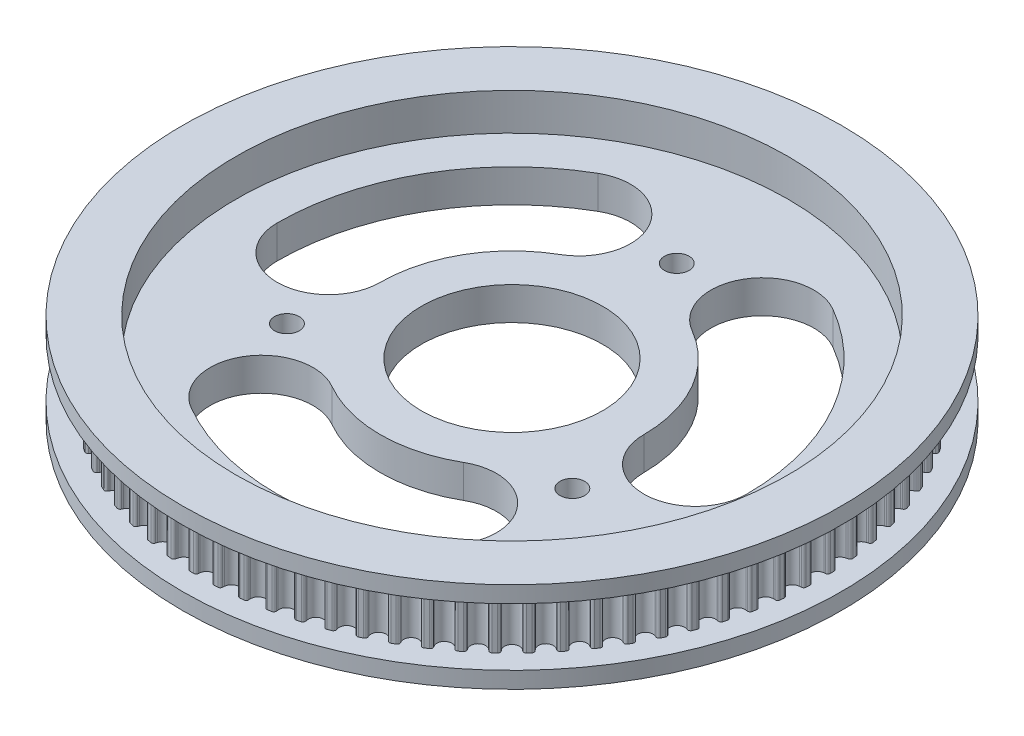
SolidWorks part; units mm, degrees
material "6061 合金"
ref_plane "前视基准面" through (0, 0, 0) normal (0, 0, 1) x (1, 0, 0)
ref_plane "上视基准面" through (0, 0, 0) normal (0, 1, 0) x (1, 0, 0)
ref_plane "右视基准面" through (0, 0, 0) normal (1, 0, 0) x (0, 0, -1)
sketch "草图1" plane through (0, 0, 0) normal (0, 1, 0) x (1, 0, 0)
  circle A0 centre (0, 0) radius 40
  dimension "D1" = 80
extrude "凸台-拉伸1" add sketch "草图1" along normal mid plane 11
sketch "草图2" plane through (0, 0, 0) normal (0, 1, 0) x (1, 0, 0)
  line L0 (0, 0) -> (0, 37.815) construction
  line L1 (-0.9274, 37.1503) -> (-0.9032, 36.9531)
  line L2 (0.9274, 37.1503) -> (0.9032, 36.9531)
  line L3 (-0.95, 37.2332) -> (0.95, 37.2332) construction
  line L4 (1.9902, 37.1086) -> (1.9989, 36.9101)
  line L5 (3.8394, 36.9631) -> (3.7997, 36.7683)
  line L6 (4.8956, 36.838) -> (4.8886, 36.6394)
  line L7 (6.7276, 36.5479) -> (6.6728, 36.3569)
  line L8 (7.7708, 36.3404) -> (7.7483, 36.1429)
  line L9 (9.5744, 35.9074) -> (9.5048, 35.7212)
  line L10 (10.598, 35.6187) -> (10.5601, 35.4236)
  line L11 (12.3621, 35.0455) -> (12.2781, 34.8654)
  line L12 (13.36, 34.6774) -> (13.3069, 34.4859)
  line L13 (15.0737, 33.9675) -> (14.9758, 33.7946)
  line L14 (16.0396, 33.5222) -> (15.9716, 33.3355)
  line L15 (17.6923, 32.6802) -> (17.5811, 32.5154)
  line L16 (18.6202, 32.1605) -> (18.5378, 31.9796)
  line L17 (20.2018, 31.1913) -> (20.0781, 31.0358)
  line L18 (21.0861, 30.6004) -> (20.9898, 30.4266)
  line L19 (22.5867, 29.5101) -> (22.4512, 29.3648)
  line L20 (23.422, 28.8517) -> (23.3123, 28.6859)
  line L21 (24.8324, 27.647) -> (24.6859, 27.5128)
  line L22 (25.6135, 26.9251) -> (25.4911, 26.7685)
  line L23 (26.9251, 25.6135) -> (26.7685, 25.4911)
  line L24 (27.647, 24.8324) -> (27.5128, 24.6859)
  line L25 (28.8517, 23.422) -> (28.6859, 23.3123)
  line L26 (29.5101, 22.5867) -> (29.3648, 22.4512)
  line L27 (30.6004, 21.0861) -> (30.4266, 20.9898)
  line L28 (31.1913, 20.2018) -> (31.0358, 20.0781)
  line L29 (32.1605, 18.6202) -> (31.9796, 18.5378)
  line L30 (32.6802, 17.6923) -> (32.5154, 17.5811)
  line L31 (33.5222, 16.0396) -> (33.3355, 15.9716)
  line L32 (33.9675, 15.0737) -> (33.7946, 14.9758)
  line L33 (34.6774, 13.36) -> (34.4859, 13.3069)
  line L34 (35.0455, 12.3621) -> (34.8654, 12.2781)
  line L35 (35.6187, 10.598) -> (35.4236, 10.5601)
  line L36 (35.9074, 9.5744) -> (35.7212, 9.5048)
  line L37 (36.3404, 7.7708) -> (36.1429, 7.7483)
  line L38 (36.5479, 6.7276) -> (36.3569, 6.6728)
  line L39 (36.838, 4.8956) -> (36.6394, 4.8886)
  line L40 (36.9631, 3.8394) -> (36.7683, 3.7997)
  line L41 (37.1086, 1.9902) -> (36.9101, 1.9989)
  line L42 (37.1503, 0.9274) -> (36.9531, 0.9032)
  line L43 (37.1503, -0.9274) -> (36.9531, -0.9032)
  line L44 (37.1086, -1.9902) -> (36.9101, -1.9989)
  line L45 (36.9631, -3.8394) -> (36.7683, -3.7997)
  line L46 (36.838, -4.8956) -> (36.6394, -4.8886)
  line L47 (36.5479, -6.7276) -> (36.3569, -6.6728)
  line L48 (36.3404, -7.7708) -> (36.1429, -7.7483)
  line L49 (35.9074, -9.5744) -> (35.7212, -9.5048)
  line L50 (35.6187, -10.598) -> (35.4236, -10.5601)
  line L51 (35.0455, -12.3621) -> (34.8654, -12.2781)
  line L52 (34.6774, -13.36) -> (34.4859, -13.3069)
  line L53 (33.9675, -15.0737) -> (33.7946, -14.9758)
  line L54 (33.5222, -16.0396) -> (33.3355, -15.9716)
  line L55 (32.6802, -17.6923) -> (32.5154, -17.5811)
  line L56 (32.1605, -18.6202) -> (31.9796, -18.5378)
  line L57 (31.1913, -20.2018) -> (31.0358, -20.0781)
  line L58 (30.6004, -21.0861) -> (30.4266, -20.9898)
  line L59 (29.5101, -22.5867) -> (29.3648, -22.4512)
  line L60 (28.8517, -23.422) -> (28.6859, -23.3123)
  line L61 (27.647, -24.8324) -> (27.5128, -24.6859)
  line L62 (26.9251, -25.6135) -> (26.7685, -25.4911)
  line L63 (25.6135, -26.9251) -> (25.4911, -26.7685)
  line L64 (24.8324, -27.647) -> (24.6859, -27.5128)
  line L65 (23.422, -28.8517) -> (23.3123, -28.6859)
  line L66 (22.5867, -29.5101) -> (22.4512, -29.3648)
  line L67 (21.0861, -30.6004) -> (20.9898, -30.4266)
  line L68 (20.2018, -31.1913) -> (20.0781, -31.0358)
  line L69 (18.6202, -32.1605) -> (18.5378, -31.9796)
  line L70 (17.6923, -32.6802) -> (17.5811, -32.5154)
  line L71 (16.0396, -33.5222) -> (15.9716, -33.3355)
  line L72 (15.0737, -33.9675) -> (14.9758, -33.7946)
  line L73 (13.36, -34.6774) -> (13.3069, -34.4859)
  line L74 (12.3621, -35.0455) -> (12.2781, -34.8654)
  line L75 (10.598, -35.6187) -> (10.5601, -35.4236)
  line L76 (9.5744, -35.9074) -> (9.5048, -35.7212)
  line L77 (7.7708, -36.3404) -> (7.7483, -36.1429)
  line L78 (6.7276, -36.5479) -> (6.6728, -36.3569)
  line L79 (4.8956, -36.838) -> (4.8886, -36.6394)
  line L80 (3.8394, -36.9631) -> (3.7997, -36.7683)
  line L81 (1.9902, -37.1086) -> (1.9989, -36.9101)
  line L82 (0.9274, -37.1503) -> (0.9032, -36.9531)
  line L83 (-0.9274, -37.1503) -> (-0.9032, -36.9531)
  line L84 (-1.9902, -37.1086) -> (-1.9989, -36.9101)
  line L85 (-3.8394, -36.9631) -> (-3.7997, -36.7683)
  line L86 (-4.8956, -36.838) -> (-4.8886, -36.6394)
  line L87 (-6.7276, -36.5479) -> (-6.6728, -36.3569)
  line L88 (-7.7708, -36.3404) -> (-7.7483, -36.1429)
  line L89 (-9.5744, -35.9074) -> (-9.5048, -35.7212)
  line L90 (-10.598, -35.6187) -> (-10.5601, -35.4236)
  line L91 (-12.3621, -35.0455) -> (-12.2781, -34.8654)
  line L92 (-13.36, -34.6774) -> (-13.3069, -34.4859)
  line L93 (-15.0737, -33.9675) -> (-14.9758, -33.7946)
  line L94 (-16.0396, -33.5222) -> (-15.9716, -33.3355)
  line L95 (-17.6923, -32.6802) -> (-17.5811, -32.5154)
  line L96 (-18.6202, -32.1605) -> (-18.5378, -31.9796)
  line L97 (-20.2018, -31.1913) -> (-20.0781, -31.0358)
  line L98 (-21.0861, -30.6004) -> (-20.9898, -30.4266)
  line L99 (-22.5867, -29.5101) -> (-22.4512, -29.3648)
  line L100 (-23.422, -28.8517) -> (-23.3123, -28.6859)
  line L101 (-24.8324, -27.647) -> (-24.6859, -27.5128)
  line L102 (-25.6135, -26.9251) -> (-25.4911, -26.7685)
  line L103 (-26.9251, -25.6135) -> (-26.7685, -25.4911)
  line L104 (-27.647, -24.8324) -> (-27.5128, -24.6859)
  line L105 (-28.8517, -23.422) -> (-28.6859, -23.3123)
  line L106 (-29.5101, -22.5867) -> (-29.3648, -22.4512)
  line L107 (-30.6004, -21.0861) -> (-30.4266, -20.9898)
  line L108 (-31.1913, -20.2018) -> (-31.0358, -20.0781)
  line L109 (-32.1605, -18.6202) -> (-31.9796, -18.5378)
  line L110 (-32.6802, -17.6923) -> (-32.5154, -17.5811)
  line L111 (-33.5222, -16.0396) -> (-33.3355, -15.9716)
  line L112 (-33.9675, -15.0737) -> (-33.7946, -14.9758)
  line L113 (-34.6774, -13.36) -> (-34.4859, -13.3069)
  line L114 (-35.0455, -12.3621) -> (-34.8654, -12.2781)
  line L115 (-35.6187, -10.598) -> (-35.4236, -10.5601)
  line L116 (-35.9074, -9.5744) -> (-35.7212, -9.5048)
  line L117 (-36.3404, -7.7708) -> (-36.1429, -7.7483)
  line L118 (-36.5479, -6.7276) -> (-36.3569, -6.6728)
  line L119 (-36.838, -4.8956) -> (-36.6394, -4.8886)
  line L120 (-36.9631, -3.8394) -> (-36.7683, -3.7997)
  line L121 (-37.1086, -1.9902) -> (-36.9101, -1.9989)
  line L122 (-37.1503, -0.9274) -> (-36.9531, -0.9032)
  line L123 (-37.1503, 0.9274) -> (-36.9531, 0.9032)
  line L124 (-37.1086, 1.9902) -> (-36.9101, 1.9989)
  line L125 (-36.9631, 3.8394) -> (-36.7683, 3.7997)
  line L126 (-36.838, 4.8956) -> (-36.6394, 4.8886)
  line L127 (-36.5479, 6.7276) -> (-36.3569, 6.6728)
  line L128 (-36.3404, 7.7708) -> (-36.1429, 7.7483)
  line L129 (-35.9074, 9.5744) -> (-35.7212, 9.5048)
  line L130 (-35.6187, 10.598) -> (-35.4236, 10.5601)
  line L131 (-35.0455, 12.3621) -> (-34.8654, 12.2781)
  line L132 (-34.6774, 13.36) -> (-34.4859, 13.3069)
  line L133 (-33.9675, 15.0737) -> (-33.7946, 14.9758)
  line L134 (-33.5222, 16.0396) -> (-33.3355, 15.9716)
  line L135 (-32.6802, 17.6923) -> (-32.5154, 17.5811)
  line L136 (-32.1605, 18.6202) -> (-31.9796, 18.5378)
  line L137 (-31.1913, 20.2018) -> (-31.0358, 20.0781)
  line L138 (-30.6004, 21.0861) -> (-30.4266, 20.9898)
  line L139 (-29.5101, 22.5867) -> (-29.3648, 22.4512)
  line L140 (-28.8517, 23.422) -> (-28.6859, 23.3123)
  line L141 (-27.647, 24.8324) -> (-27.5128, 24.6859)
  line L142 (-26.9251, 25.6135) -> (-26.7685, 25.4911)
  line L143 (-25.6135, 26.9251) -> (-25.4911, 26.7685)
  line L144 (-24.8324, 27.647) -> (-24.6859, 27.5128)
  line L145 (-23.422, 28.8517) -> (-23.3123, 28.6859)
  line L146 (-22.5867, 29.5101) -> (-22.4512, 29.3648)
  line L147 (-21.0861, 30.6004) -> (-20.9898, 30.4266)
  line L148 (-20.2018, 31.1913) -> (-20.0781, 31.0358)
  line L149 (-18.6202, 32.1605) -> (-18.5378, 31.9796)
  line L150 (-17.6923, 32.6802) -> (-17.5811, 32.5154)
  line L151 (-16.0396, 33.5222) -> (-15.9716, 33.3355)
  line L152 (-15.0737, 33.9675) -> (-14.9758, 33.7946)
  line L153 (-13.36, 34.6774) -> (-13.3069, 34.4859)
  line L154 (-12.3621, 35.0455) -> (-12.2781, 34.8654)
  line L155 (-10.598, 35.6187) -> (-10.5601, 35.4236)
  line L156 (-9.5744, 35.9074) -> (-9.5048, 35.7212)
  line L157 (-7.7708, 36.3404) -> (-7.7483, 36.1429)
  line L158 (-6.7276, 36.5479) -> (-6.6728, 36.3569)
  line L159 (-4.8956, 36.838) -> (-4.8886, 36.6394)
  line L160 (-3.8394, 36.9631) -> (-3.7997, 36.7683)
  line L161 (-1.9902, 37.1086) -> (-1.9989, 36.9101)
  arc A0 (-1.2351, 37.4136) -> (-1.7041, 37.3952) centre (0, 0) ccw
  arc A1 (1.7041, 37.3952) -> (1.2351, 37.4136) centre (0, 0) ccw
  arc A3 (-0.9032, 36.9531) -> (0.9032, 36.9531) centre (0, 37.064) ccw
  arc A4 (-0.9274, 37.1503) -> (-1.2351, 37.4136) centre (-1.2252, 37.1138) ccw
  arc A5 (0.9274, 37.1503) -> (1.2351, 37.4136) centre (1.2252, 37.1138) cw
  arc A6 (1.9902, 37.1086) -> (1.7041, 37.3952) centre (1.6905, 37.0955) ccw
  arc A7 (1.9989, 36.9101) -> (3.7997, 36.7683) centre (2.908, 36.9497) ccw
  arc A8 (3.8394, 36.9631) -> (4.1667, 37.2014) centre (4.1333, 36.9032) cw
  arc A9 (4.6329, 37.1462) -> (4.1667, 37.2014) centre (0, 0) ccw
  arc A10 (4.8956, 36.838) -> (4.6329, 37.1462) centre (4.5958, 36.8485) ccw
  arc A11 (4.8886, 36.6394) -> (6.6728, 36.3569) centre (5.7981, 36.6077) ccw
  arc A12 (6.7276, 36.5479) -> (7.0727, 36.7598) centre (7.016, 36.4652) cw
  arc A13 (7.5331, 36.6682) -> (7.0727, 36.7598) centre (0, 0) ccw
  arc A14 (7.7708, 36.3404) -> (7.5331, 36.6682) centre (7.4727, 36.3743) ccw
  arc A15 (7.7483, 36.1429) -> (9.5048, 35.7212) centre (8.6524, 36.0399) ccw
  arc A16 (9.5744, 35.9074) -> (9.935, 36.0915) centre (9.8554, 35.8023) cw
  arc A17 (10.3868, 35.9641) -> (9.935, 36.0915) centre (0, 0) ccw
  arc A18 (10.598, 35.6187) -> (10.3868, 35.9641) centre (10.3036, 35.6759) ccw
  arc A19 (10.5601, 35.4236) -> (12.2781, 34.8654) centre (11.4534, 35.25) ccw
  arc A20 (12.3621, 35.0455) -> (12.7361, 35.2008) centre (12.634, 34.9187) cw
  arc A21 (13.1765, 35.0383) -> (12.7361, 35.2008) centre (0, 0) ccw
  arc A22 (13.36, 34.6774) -> (13.1765, 35.0383) centre (13.0709, 34.7575) ccw
  arc A23 (13.3069, 34.4859) -> (14.9758, 33.7946) centre (14.1838, 34.2427) ccw
  arc A24 (15.0737, 33.9675) -> (15.4587, 34.093) centre (15.3348, 33.8198) cw
  arc A25 (15.8849, 33.8965) -> (15.4587, 34.093) centre (0, 0) ccw
  arc A26 (16.0396, 33.5222) -> (15.8849, 33.8965) centre (15.7576, 33.6249) ccw
  arc A27 (15.9716, 33.3355) -> (17.5811, 32.5154) centre (16.8267, 33.0243) ccw
  arc A28 (17.6923, 32.6802) -> (18.0859, 32.7751) centre (17.941, 32.5124) cw
  arc A29 (18.4955, 32.5457) -> (18.0859, 32.7751) centre (0, 0) ccw
  arc A30 (18.6202, 32.1605) -> (18.4955, 32.5457) centre (18.3472, 32.2849) ccw
  arc A31 (18.5378, 31.9796) -> (20.0781, 31.0358) centre (19.3659, 31.6023) ccw
  arc A32 (20.2018, 31.1913) -> (20.6017, 31.255) centre (20.4366, 31.0045) cw
  arc A33 (20.992, 30.9942) -> (20.6017, 31.255) centre (0, 0) ccw
  arc A34 (21.0861, 30.6004) -> (20.992, 30.9942) centre (20.8237, 30.7458) ccw
  arc A35 (20.9898, 30.4266) -> (22.4512, 29.3648) centre (21.7857, 29.9854) ccw
  arc A36 (22.5867, 29.5101) -> (22.9904, 29.5423) centre (22.8061, 29.3055) cw
  arc A37 (23.359, 29.2517) -> (22.9904, 29.5423) centre (0, 0) ccw
  arc A38 (23.422, 28.8517) -> (23.359, 29.2517) centre (23.1718, 29.0172) ccw
  arc A39 (23.3123, 28.6859) -> (24.6859, 27.5128) centre (24.0711, 28.1837) ccw
  arc A40 (24.8324, 27.647) -> (25.2374, 27.6474) centre (25.0351, 27.4258) cw
  arc A41 (25.5821, 27.3288) -> (25.2374, 27.6474) centre (0, 0) ccw
  arc A42 (25.6135, 26.9251) -> (25.5821, 27.3288) centre (25.3771, 27.1098) ccw
  arc A43 (25.4911, 26.7685) -> (26.7685, 25.4911) centre (26.2082, 26.2082) ccw
  arc A44 (26.9251, 25.6135) -> (27.3288, 25.5821) centre (27.1098, 25.3771) cw
  arc A45 (27.6474, 25.2374) -> (27.3288, 25.5821) centre (0, 0) ccw
  arc A46 (27.647, 24.8324) -> (27.6474, 25.2374) centre (27.4258, 25.0351) ccw
  arc A47 (27.5128, 24.6859) -> (28.6859, 23.3123) centre (28.1837, 24.0711) ccw
  arc A48 (28.8517, 23.422) -> (29.2517, 23.359) centre (29.0172, 23.1718) cw
  arc A49 (29.5423, 22.9904) -> (29.2517, 23.359) centre (0, 0) ccw
  arc A50 (29.5101, 22.5867) -> (29.5423, 22.9904) centre (29.3055, 22.8061) ccw
  arc A51 (29.3648, 22.4512) -> (30.4266, 20.9898) centre (29.9854, 21.7857) ccw
  arc A52 (30.6004, 21.0861) -> (30.9942, 20.992) centre (30.7458, 20.8237) cw
  arc A53 (31.255, 20.6017) -> (30.9942, 20.992) centre (0, 0) ccw
  arc A54 (31.1913, 20.2018) -> (31.255, 20.6017) centre (31.0045, 20.4366) ccw
  arc A55 (31.0358, 20.0781) -> (31.9796, 18.5378) centre (31.6023, 19.3659) ccw
  arc A56 (32.1605, 18.6202) -> (32.5457, 18.4955) centre (32.2849, 18.3472) cw
  arc A57 (32.7751, 18.0859) -> (32.5457, 18.4955) centre (0, 0) ccw
  arc A58 (32.6802, 17.6923) -> (32.7751, 18.0859) centre (32.5124, 17.941) ccw
  arc A59 (32.5154, 17.5811) -> (33.3355, 15.9716) centre (33.0243, 16.8267) ccw
  arc A60 (33.5222, 16.0396) -> (33.8965, 15.8849) centre (33.6249, 15.7576) cw
  arc A61 (34.093, 15.4587) -> (33.8965, 15.8849) centre (0, 0) ccw
  arc A62 (33.9675, 15.0737) -> (34.093, 15.4587) centre (33.8198, 15.3348) ccw
  arc A63 (33.7946, 14.9758) -> (34.4859, 13.3069) centre (34.2427, 14.1838) ccw
  arc A64 (34.6774, 13.36) -> (35.0383, 13.1765) centre (34.7575, 13.0709) cw
  arc A65 (35.2008, 12.7361) -> (35.0383, 13.1765) centre (0, 0) ccw
  arc A66 (35.0455, 12.3621) -> (35.2008, 12.7361) centre (34.9187, 12.634) ccw
  arc A67 (34.8654, 12.2781) -> (35.4236, 10.5601) centre (35.25, 11.4534) ccw
  arc A68 (35.6187, 10.598) -> (35.9641, 10.3868) centre (35.6759, 10.3036) cw
  arc A69 (36.0915, 9.935) -> (35.9641, 10.3868) centre (0, 0) ccw
  arc A70 (35.9074, 9.5744) -> (36.0915, 9.935) centre (35.8023, 9.8554) ccw
  arc A71 (35.7212, 9.5048) -> (36.1429, 7.7483) centre (36.0399, 8.6524) ccw
  arc A72 (36.3404, 7.7708) -> (36.6682, 7.5331) centre (36.3743, 7.4727) cw
  arc A73 (36.7598, 7.0727) -> (36.6682, 7.5331) centre (0, 0) ccw
  arc A74 (36.5479, 6.7276) -> (36.7598, 7.0727) centre (36.4652, 7.016) ccw
  arc A75 (36.3569, 6.6728) -> (36.6394, 4.8886) centre (36.6077, 5.7981) ccw
  arc A76 (36.838, 4.8956) -> (37.1462, 4.6329) centre (36.8485, 4.5958) cw
  arc A77 (37.2014, 4.1667) -> (37.1462, 4.6329) centre (0, 0) ccw
  arc A78 (36.9631, 3.8394) -> (37.2014, 4.1667) centre (36.9032, 4.1333) ccw
  arc A79 (36.7683, 3.7997) -> (36.9101, 1.9989) centre (36.9497, 2.908) ccw
  arc A80 (37.1086, 1.9902) -> (37.3952, 1.7041) centre (37.0955, 1.6905) cw
  arc A81 (37.4136, 1.2351) -> (37.3952, 1.7041) centre (0, 0) ccw
  arc A82 (37.1503, 0.9274) -> (37.4136, 1.2351) centre (37.1138, 1.2252) ccw
  arc A83 (36.9531, 0.9032) -> (36.9531, -0.9032) centre (37.064, 0) ccw
  arc A84 (37.1503, -0.9274) -> (37.4136, -1.2351) centre (37.1138, -1.2252) cw
  arc A85 (37.3952, -1.7041) -> (37.4136, -1.2351) centre (0, 0) ccw
  arc A86 (37.1086, -1.9902) -> (37.3952, -1.7041) centre (37.0955, -1.6905) ccw
  arc A87 (36.9101, -1.9989) -> (36.7683, -3.7997) centre (36.9497, -2.908) ccw
  arc A88 (36.9631, -3.8394) -> (37.2014, -4.1667) centre (36.9032, -4.1333) cw
  arc A89 (37.1462, -4.6329) -> (37.2014, -4.1667) centre (0, 0) ccw
  arc A90 (36.838, -4.8956) -> (37.1462, -4.6329) centre (36.8485, -4.5958) ccw
  arc A91 (36.6394, -4.8886) -> (36.3569, -6.6728) centre (36.6077, -5.7981) ccw
  arc A92 (36.5479, -6.7276) -> (36.7598, -7.0727) centre (36.4652, -7.016) cw
  arc A93 (36.6682, -7.5331) -> (36.7598, -7.0727) centre (0, 0) ccw
  arc A94 (36.3404, -7.7708) -> (36.6682, -7.5331) centre (36.3743, -7.4727) ccw
  arc A95 (36.1429, -7.7483) -> (35.7212, -9.5048) centre (36.0399, -8.6524) ccw
  arc A96 (35.9074, -9.5744) -> (36.0915, -9.935) centre (35.8023, -9.8554) cw
  arc A97 (35.9641, -10.3868) -> (36.0915, -9.935) centre (0, 0) ccw
  arc A98 (35.6187, -10.598) -> (35.9641, -10.3868) centre (35.6759, -10.3036) ccw
  arc A99 (35.4236, -10.5601) -> (34.8654, -12.2781) centre (35.25, -11.4534) ccw
  arc A100 (35.0455, -12.3621) -> (35.2008, -12.7361) centre (34.9187, -12.634) cw
  arc A101 (35.0383, -13.1765) -> (35.2008, -12.7361) centre (0, 0) ccw
  arc A102 (34.6774, -13.36) -> (35.0383, -13.1765) centre (34.7575, -13.0709) ccw
  arc A103 (34.4859, -13.3069) -> (33.7946, -14.9758) centre (34.2427, -14.1838) ccw
  arc A104 (33.9675, -15.0737) -> (34.093, -15.4587) centre (33.8198, -15.3348) cw
  arc A105 (33.8965, -15.8849) -> (34.093, -15.4587) centre (0, 0) ccw
  arc A106 (33.5222, -16.0396) -> (33.8965, -15.8849) centre (33.6249, -15.7576) ccw
  arc A107 (33.3355, -15.9716) -> (32.5154, -17.5811) centre (33.0243, -16.8267) ccw
  arc A108 (32.6802, -17.6923) -> (32.7751, -18.0859) centre (32.5124, -17.941) cw
  arc A109 (32.5457, -18.4955) -> (32.7751, -18.0859) centre (0, 0) ccw
  arc A110 (32.1605, -18.6202) -> (32.5457, -18.4955) centre (32.2849, -18.3472) ccw
  arc A111 (31.9796, -18.5378) -> (31.0358, -20.0781) centre (31.6023, -19.3659) ccw
  arc A112 (31.1913, -20.2018) -> (31.255, -20.6017) centre (31.0045, -20.4366) cw
  arc A113 (30.9942, -20.992) -> (31.255, -20.6017) centre (0, 0) ccw
  arc A114 (30.6004, -21.0861) -> (30.9942, -20.992) centre (30.7458, -20.8237) ccw
  arc A115 (30.4266, -20.9898) -> (29.3648, -22.4512) centre (29.9854, -21.7857) ccw
  arc A116 (29.5101, -22.5867) -> (29.5423, -22.9904) centre (29.3055, -22.8061) cw
  arc A117 (29.2517, -23.359) -> (29.5423, -22.9904) centre (0, 0) ccw
  arc A118 (28.8517, -23.422) -> (29.2517, -23.359) centre (29.0172, -23.1718) ccw
  arc A119 (28.6859, -23.3123) -> (27.5128, -24.6859) centre (28.1837, -24.0711) ccw
  arc A120 (27.647, -24.8324) -> (27.6474, -25.2374) centre (27.4258, -25.0351) cw
  arc A121 (27.3288, -25.5821) -> (27.6474, -25.2374) centre (0, 0) ccw
  arc A122 (26.9251, -25.6135) -> (27.3288, -25.5821) centre (27.1098, -25.3771) ccw
  arc A123 (26.7685, -25.4911) -> (25.4911, -26.7685) centre (26.2082, -26.2082) ccw
  arc A124 (25.6135, -26.9251) -> (25.5821, -27.3288) centre (25.3771, -27.1098) cw
  arc A125 (25.2374, -27.6474) -> (25.5821, -27.3288) centre (0, 0) ccw
  arc A126 (24.8324, -27.647) -> (25.2374, -27.6474) centre (25.0351, -27.4258) ccw
  arc A127 (24.6859, -27.5128) -> (23.3123, -28.6859) centre (24.0711, -28.1837) ccw
  arc A128 (23.422, -28.8517) -> (23.359, -29.2517) centre (23.1718, -29.0172) cw
  arc A129 (22.9904, -29.5423) -> (23.359, -29.2517) centre (0, 0) ccw
  arc A130 (22.5867, -29.5101) -> (22.9904, -29.5423) centre (22.8061, -29.3055) ccw
  arc A131 (22.4512, -29.3648) -> (20.9898, -30.4266) centre (21.7857, -29.9854) ccw
  arc A132 (21.0861, -30.6004) -> (20.992, -30.9942) centre (20.8237, -30.7458) cw
  arc A133 (20.6017, -31.255) -> (20.992, -30.9942) centre (0, 0) ccw
  arc A134 (20.2018, -31.1913) -> (20.6017, -31.255) centre (20.4366, -31.0045) ccw
  arc A135 (20.0781, -31.0358) -> (18.5378, -31.9796) centre (19.3659, -31.6023) ccw
  arc A136 (18.6202, -32.1605) -> (18.4955, -32.5457) centre (18.3472, -32.2849) cw
  arc A137 (18.0859, -32.7751) -> (18.4955, -32.5457) centre (0, 0) ccw
  arc A138 (17.6923, -32.6802) -> (18.0859, -32.7751) centre (17.941, -32.5124) ccw
  arc A139 (17.5811, -32.5154) -> (15.9716, -33.3355) centre (16.8267, -33.0243) ccw
  arc A140 (16.0396, -33.5222) -> (15.8849, -33.8965) centre (15.7576, -33.6249) cw
  arc A141 (15.4587, -34.093) -> (15.8849, -33.8965) centre (0, 0) ccw
  arc A142 (15.0737, -33.9675) -> (15.4587, -34.093) centre (15.3348, -33.8198) ccw
  arc A143 (14.9758, -33.7946) -> (13.3069, -34.4859) centre (14.1838, -34.2427) ccw
  arc A144 (13.36, -34.6774) -> (13.1765, -35.0383) centre (13.0709, -34.7575) cw
  arc A145 (12.7361, -35.2008) -> (13.1765, -35.0383) centre (0, 0) ccw
  arc A146 (12.3621, -35.0455) -> (12.7361, -35.2008) centre (12.634, -34.9187) ccw
  arc A147 (12.2781, -34.8654) -> (10.5601, -35.4236) centre (11.4534, -35.25) ccw
  arc A148 (10.598, -35.6187) -> (10.3868, -35.9641) centre (10.3036, -35.6759) cw
  arc A149 (9.935, -36.0915) -> (10.3868, -35.9641) centre (0, 0) ccw
  arc A150 (9.5744, -35.9074) -> (9.935, -36.0915) centre (9.8554, -35.8023) ccw
  arc A151 (9.5048, -35.7212) -> (7.7483, -36.1429) centre (8.6524, -36.0399) ccw
  arc A152 (7.7708, -36.3404) -> (7.5331, -36.6682) centre (7.4727, -36.3743) cw
  arc A153 (7.0727, -36.7598) -> (7.5331, -36.6682) centre (0, 0) ccw
  arc A154 (6.7276, -36.5479) -> (7.0727, -36.7598) centre (7.016, -36.4652) ccw
  arc A155 (6.6728, -36.3569) -> (4.8886, -36.6394) centre (5.7981, -36.6077) ccw
  arc A156 (4.8956, -36.838) -> (4.6329, -37.1462) centre (4.5958, -36.8485) cw
  arc A157 (4.1667, -37.2014) -> (4.6329, -37.1462) centre (0, 0) ccw
  arc A158 (3.8394, -36.9631) -> (4.1667, -37.2014) centre (4.1333, -36.9032) ccw
  arc A159 (3.7997, -36.7683) -> (1.9989, -36.9101) centre (2.908, -36.9497) ccw
  arc A160 (1.9902, -37.1086) -> (1.7041, -37.3952) centre (1.6905, -37.0955) cw
  arc A161 (1.2351, -37.4136) -> (1.7041, -37.3952) centre (0, 0) ccw
  arc A162 (0.9274, -37.1503) -> (1.2351, -37.4136) centre (1.2252, -37.1138) ccw
  arc A163 (0.9032, -36.9531) -> (-0.9032, -36.9531) centre (0, -37.064) ccw
  arc A164 (-0.9274, -37.1503) -> (-1.2351, -37.4136) centre (-1.2252, -37.1138) cw
  arc A165 (-1.7041, -37.3952) -> (-1.2351, -37.4136) centre (0, 0) ccw
  arc A166 (-1.9902, -37.1086) -> (-1.7041, -37.3952) centre (-1.6905, -37.0955) ccw
  arc A167 (-1.9989, -36.9101) -> (-3.7997, -36.7683) centre (-2.908, -36.9497) ccw
  arc A168 (-3.8394, -36.9631) -> (-4.1667, -37.2014) centre (-4.1333, -36.9032) cw
  arc A169 (-4.6329, -37.1462) -> (-4.1667, -37.2014) centre (0, 0) ccw
  arc A170 (-4.8956, -36.838) -> (-4.6329, -37.1462) centre (-4.5958, -36.8485) ccw
  arc A171 (-4.8886, -36.6394) -> (-6.6728, -36.3569) centre (-5.7981, -36.6077) ccw
  arc A172 (-6.7276, -36.5479) -> (-7.0727, -36.7598) centre (-7.016, -36.4652) cw
  arc A173 (-7.5331, -36.6682) -> (-7.0727, -36.7598) centre (0, 0) ccw
  arc A174 (-7.7708, -36.3404) -> (-7.5331, -36.6682) centre (-7.4727, -36.3743) ccw
  arc A175 (-7.7483, -36.1429) -> (-9.5048, -35.7212) centre (-8.6524, -36.0399) ccw
  arc A176 (-9.5744, -35.9074) -> (-9.935, -36.0915) centre (-9.8554, -35.8023) cw
  arc A177 (-10.3868, -35.9641) -> (-9.935, -36.0915) centre (0, 0) ccw
  arc A178 (-10.598, -35.6187) -> (-10.3868, -35.9641) centre (-10.3036, -35.6759) ccw
  arc A179 (-10.5601, -35.4236) -> (-12.2781, -34.8654) centre (-11.4534, -35.25) ccw
  arc A180 (-12.3621, -35.0455) -> (-12.7361, -35.2008) centre (-12.634, -34.9187) cw
  arc A181 (-13.1765, -35.0383) -> (-12.7361, -35.2008) centre (0, 0) ccw
  arc A182 (-13.36, -34.6774) -> (-13.1765, -35.0383) centre (-13.0709, -34.7575) ccw
  arc A183 (-13.3069, -34.4859) -> (-14.9758, -33.7946) centre (-14.1838, -34.2427) ccw
  arc A184 (-15.0737, -33.9675) -> (-15.4587, -34.093) centre (-15.3348, -33.8198) cw
  arc A185 (-15.8849, -33.8965) -> (-15.4587, -34.093) centre (0, 0) ccw
  arc A186 (-16.0396, -33.5222) -> (-15.8849, -33.8965) centre (-15.7576, -33.6249) ccw
  arc A187 (-15.9716, -33.3355) -> (-17.5811, -32.5154) centre (-16.8267, -33.0243) ccw
  arc A188 (-17.6923, -32.6802) -> (-18.0859, -32.7751) centre (-17.941, -32.5124) cw
  arc A189 (-18.4955, -32.5457) -> (-18.0859, -32.7751) centre (0, 0) ccw
  arc A190 (-18.6202, -32.1605) -> (-18.4955, -32.5457) centre (-18.3472, -32.2849) ccw
  arc A191 (-18.5378, -31.9796) -> (-20.0781, -31.0358) centre (-19.3659, -31.6023) ccw
  arc A192 (-20.2018, -31.1913) -> (-20.6017, -31.255) centre (-20.4366, -31.0045) cw
  arc A193 (-20.992, -30.9942) -> (-20.6017, -31.255) centre (0, 0) ccw
  arc A194 (-21.0861, -30.6004) -> (-20.992, -30.9942) centre (-20.8237, -30.7458) ccw
  arc A195 (-20.9898, -30.4266) -> (-22.4512, -29.3648) centre (-21.7857, -29.9854) ccw
  arc A196 (-22.5867, -29.5101) -> (-22.9904, -29.5423) centre (-22.8061, -29.3055) cw
  arc A197 (-23.359, -29.2517) -> (-22.9904, -29.5423) centre (0, 0) ccw
  arc A198 (-23.422, -28.8517) -> (-23.359, -29.2517) centre (-23.1718, -29.0172) ccw
  arc A199 (-23.3123, -28.6859) -> (-24.6859, -27.5128) centre (-24.0711, -28.1837) ccw
  arc A200 (-24.8324, -27.647) -> (-25.2374, -27.6474) centre (-25.0351, -27.4258) cw
  arc A201 (-25.5821, -27.3288) -> (-25.2374, -27.6474) centre (0, 0) ccw
  arc A202 (-25.6135, -26.9251) -> (-25.5821, -27.3288) centre (-25.3771, -27.1098) ccw
  arc A203 (-25.4911, -26.7685) -> (-26.7685, -25.4911) centre (-26.2082, -26.2082) ccw
  arc A204 (-26.9251, -25.6135) -> (-27.3288, -25.5821) centre (-27.1098, -25.3771) cw
  arc A205 (-27.6474, -25.2374) -> (-27.3288, -25.5821) centre (0, 0) ccw
  arc A206 (-27.647, -24.8324) -> (-27.6474, -25.2374) centre (-27.4258, -25.0351) ccw
  arc A207 (-27.5128, -24.6859) -> (-28.6859, -23.3123) centre (-28.1837, -24.0711) ccw
  arc A208 (-28.8517, -23.422) -> (-29.2517, -23.359) centre (-29.0172, -23.1718) cw
  arc A209 (-29.5423, -22.9904) -> (-29.2517, -23.359) centre (0, 0) ccw
  arc A210 (-29.5101, -22.5867) -> (-29.5423, -22.9904) centre (-29.3055, -22.8061) ccw
  arc A211 (-29.3648, -22.4512) -> (-30.4266, -20.9898) centre (-29.9854, -21.7857) ccw
  arc A212 (-30.6004, -21.0861) -> (-30.9942, -20.992) centre (-30.7458, -20.8237) cw
  arc A213 (-31.255, -20.6017) -> (-30.9942, -20.992) centre (0, 0) ccw
  arc A214 (-31.1913, -20.2018) -> (-31.255, -20.6017) centre (-31.0045, -20.4366) ccw
  arc A215 (-31.0358, -20.0781) -> (-31.9796, -18.5378) centre (-31.6023, -19.3659) ccw
  arc A216 (-32.1605, -18.6202) -> (-32.5457, -18.4955) centre (-32.2849, -18.3472) cw
  arc A217 (-32.7751, -18.0859) -> (-32.5457, -18.4955) centre (0, 0) ccw
  arc A218 (-32.6802, -17.6923) -> (-32.7751, -18.0859) centre (-32.5124, -17.941) ccw
  arc A219 (-32.5154, -17.5811) -> (-33.3355, -15.9716) centre (-33.0243, -16.8267) ccw
  arc A220 (-33.5222, -16.0396) -> (-33.8965, -15.8849) centre (-33.6249, -15.7576) cw
  arc A221 (-34.093, -15.4587) -> (-33.8965, -15.8849) centre (0, 0) ccw
  arc A222 (-33.9675, -15.0737) -> (-34.093, -15.4587) centre (-33.8198, -15.3348) ccw
  arc A223 (-33.7946, -14.9758) -> (-34.4859, -13.3069) centre (-34.2427, -14.1838) ccw
  arc A224 (-34.6774, -13.36) -> (-35.0383, -13.1765) centre (-34.7575, -13.0709) cw
  arc A225 (-35.2008, -12.7361) -> (-35.0383, -13.1765) centre (0, 0) ccw
  arc A226 (-35.0455, -12.3621) -> (-35.2008, -12.7361) centre (-34.9187, -12.634) ccw
  arc A227 (-34.8654, -12.2781) -> (-35.4236, -10.5601) centre (-35.25, -11.4534) ccw
  arc A228 (-35.6187, -10.598) -> (-35.9641, -10.3868) centre (-35.6759, -10.3036) cw
  arc A229 (-36.0915, -9.935) -> (-35.9641, -10.3868) centre (0, 0) ccw
  arc A230 (-35.9074, -9.5744) -> (-36.0915, -9.935) centre (-35.8023, -9.8554) ccw
  arc A231 (-35.7212, -9.5048) -> (-36.1429, -7.7483) centre (-36.0399, -8.6524) ccw
  arc A232 (-36.3404, -7.7708) -> (-36.6682, -7.5331) centre (-36.3743, -7.4727) cw
  arc A233 (-36.7598, -7.0727) -> (-36.6682, -7.5331) centre (0, 0) ccw
  arc A234 (-36.5479, -6.7276) -> (-36.7598, -7.0727) centre (-36.4652, -7.016) ccw
  arc A235 (-36.3569, -6.6728) -> (-36.6394, -4.8886) centre (-36.6077, -5.7981) ccw
  arc A236 (-36.838, -4.8956) -> (-37.1462, -4.6329) centre (-36.8485, -4.5958) cw
  arc A237 (-37.2014, -4.1667) -> (-37.1462, -4.6329) centre (0, 0) ccw
  arc A238 (-36.9631, -3.8394) -> (-37.2014, -4.1667) centre (-36.9032, -4.1333) ccw
  arc A239 (-36.7683, -3.7997) -> (-36.9101, -1.9989) centre (-36.9497, -2.908) ccw
  arc A240 (-37.1086, -1.9902) -> (-37.3952, -1.7041) centre (-37.0955, -1.6905) cw
  arc A241 (-37.4136, -1.2351) -> (-37.3952, -1.7041) centre (0, 0) ccw
  arc A242 (-37.1503, -0.9274) -> (-37.4136, -1.2351) centre (-37.1138, -1.2252) ccw
  arc A243 (-36.9531, -0.9032) -> (-36.9531, 0.9032) centre (-37.064, 0) ccw
  arc A244 (-37.1503, 0.9274) -> (-37.4136, 1.2351) centre (-37.1138, 1.2252) cw
  arc A245 (-37.3952, 1.7041) -> (-37.4136, 1.2351) centre (0, 0) ccw
  arc A246 (-37.1086, 1.9902) -> (-37.3952, 1.7041) centre (-37.0955, 1.6905) ccw
  arc A247 (-36.9101, 1.9989) -> (-36.7683, 3.7997) centre (-36.9497, 2.908) ccw
  arc A248 (-36.9631, 3.8394) -> (-37.2014, 4.1667) centre (-36.9032, 4.1333) cw
  arc A249 (-37.1462, 4.6329) -> (-37.2014, 4.1667) centre (0, 0) ccw
  arc A250 (-36.838, 4.8956) -> (-37.1462, 4.6329) centre (-36.8485, 4.5958) ccw
  arc A251 (-36.6394, 4.8886) -> (-36.3569, 6.6728) centre (-36.6077, 5.7981) ccw
  arc A252 (-36.5479, 6.7276) -> (-36.7598, 7.0727) centre (-36.4652, 7.016) cw
  arc A253 (-36.6682, 7.5331) -> (-36.7598, 7.0727) centre (0, 0) ccw
  arc A254 (-36.3404, 7.7708) -> (-36.6682, 7.5331) centre (-36.3743, 7.4727) ccw
  arc A255 (-36.1429, 7.7483) -> (-35.7212, 9.5048) centre (-36.0399, 8.6524) ccw
  arc A256 (-35.9074, 9.5744) -> (-36.0915, 9.935) centre (-35.8023, 9.8554) cw
  arc A257 (-35.9641, 10.3868) -> (-36.0915, 9.935) centre (0, 0) ccw
  arc A258 (-35.6187, 10.598) -> (-35.9641, 10.3868) centre (-35.6759, 10.3036) ccw
  arc A259 (-35.4236, 10.5601) -> (-34.8654, 12.2781) centre (-35.25, 11.4534) ccw
  arc A260 (-35.0455, 12.3621) -> (-35.2008, 12.7361) centre (-34.9187, 12.634) cw
  arc A261 (-35.0383, 13.1765) -> (-35.2008, 12.7361) centre (0, 0) ccw
  arc A262 (-34.6774, 13.36) -> (-35.0383, 13.1765) centre (-34.7575, 13.0709) ccw
  arc A263 (-34.4859, 13.3069) -> (-33.7946, 14.9758) centre (-34.2427, 14.1838) ccw
  arc A264 (-33.9675, 15.0737) -> (-34.093, 15.4587) centre (-33.8198, 15.3348) cw
  arc A265 (-33.8965, 15.8849) -> (-34.093, 15.4587) centre (0, 0) ccw
  arc A266 (-33.5222, 16.0396) -> (-33.8965, 15.8849) centre (-33.6249, 15.7576) ccw
  arc A267 (-33.3355, 15.9716) -> (-32.5154, 17.5811) centre (-33.0243, 16.8267) ccw
  arc A268 (-32.6802, 17.6923) -> (-32.7751, 18.0859) centre (-32.5124, 17.941) cw
  arc A269 (-32.5457, 18.4955) -> (-32.7751, 18.0859) centre (0, 0) ccw
  arc A270 (-32.1605, 18.6202) -> (-32.5457, 18.4955) centre (-32.2849, 18.3472) ccw
  arc A271 (-31.9796, 18.5378) -> (-31.0358, 20.0781) centre (-31.6023, 19.3659) ccw
  arc A272 (-31.1913, 20.2018) -> (-31.255, 20.6017) centre (-31.0045, 20.4366) cw
  arc A273 (-30.9942, 20.992) -> (-31.255, 20.6017) centre (0, 0) ccw
  arc A274 (-30.6004, 21.0861) -> (-30.9942, 20.992) centre (-30.7458, 20.8237) ccw
  arc A275 (-30.4266, 20.9898) -> (-29.3648, 22.4512) centre (-29.9854, 21.7857) ccw
  arc A276 (-29.5101, 22.5867) -> (-29.5423, 22.9904) centre (-29.3055, 22.8061) cw
  arc A277 (-29.2517, 23.359) -> (-29.5423, 22.9904) centre (0, 0) ccw
  arc A278 (-28.8517, 23.422) -> (-29.2517, 23.359) centre (-29.0172, 23.1718) ccw
  arc A279 (-28.6859, 23.3123) -> (-27.5128, 24.6859) centre (-28.1837, 24.0711) ccw
  arc A280 (-27.647, 24.8324) -> (-27.6474, 25.2374) centre (-27.4258, 25.0351) cw
  arc A281 (-27.3288, 25.5821) -> (-27.6474, 25.2374) centre (0, 0) ccw
  arc A282 (-26.9251, 25.6135) -> (-27.3288, 25.5821) centre (-27.1098, 25.3771) ccw
  arc A283 (-26.7685, 25.4911) -> (-25.4911, 26.7685) centre (-26.2082, 26.2082) ccw
  arc A284 (-25.6135, 26.9251) -> (-25.5821, 27.3288) centre (-25.3771, 27.1098) cw
  arc A285 (-25.2374, 27.6474) -> (-25.5821, 27.3288) centre (0, 0) ccw
  arc A286 (-24.8324, 27.647) -> (-25.2374, 27.6474) centre (-25.0351, 27.4258) ccw
  arc A287 (-24.6859, 27.5128) -> (-23.3123, 28.6859) centre (-24.0711, 28.1837) ccw
  arc A288 (-23.422, 28.8517) -> (-23.359, 29.2517) centre (-23.1718, 29.0172) cw
  arc A289 (-22.9904, 29.5423) -> (-23.359, 29.2517) centre (0, 0) ccw
  arc A290 (-22.5867, 29.5101) -> (-22.9904, 29.5423) centre (-22.8061, 29.3055) ccw
  arc A291 (-22.4512, 29.3648) -> (-20.9898, 30.4266) centre (-21.7857, 29.9854) ccw
  arc A292 (-21.0861, 30.6004) -> (-20.992, 30.9942) centre (-20.8237, 30.7458) cw
  arc A293 (-20.6017, 31.255) -> (-20.992, 30.9942) centre (0, 0) ccw
  arc A294 (-20.2018, 31.1913) -> (-20.6017, 31.255) centre (-20.4366, 31.0045) ccw
  arc A295 (-20.0781, 31.0358) -> (-18.5378, 31.9796) centre (-19.3659, 31.6023) ccw
  arc A296 (-18.6202, 32.1605) -> (-18.4955, 32.5457) centre (-18.3472, 32.2849) cw
  arc A297 (-18.0859, 32.7751) -> (-18.4955, 32.5457) centre (0, 0) ccw
  arc A298 (-17.6923, 32.6802) -> (-18.0859, 32.7751) centre (-17.941, 32.5124) ccw
  arc A299 (-17.5811, 32.5154) -> (-15.9716, 33.3355) centre (-16.8267, 33.0243) ccw
  arc A300 (-16.0396, 33.5222) -> (-15.8849, 33.8965) centre (-15.7576, 33.6249) cw
  arc A301 (-15.4587, 34.093) -> (-15.8849, 33.8965) centre (0, 0) ccw
  arc A302 (-15.0737, 33.9675) -> (-15.4587, 34.093) centre (-15.3348, 33.8198) ccw
  arc A303 (-14.9758, 33.7946) -> (-13.3069, 34.4859) centre (-14.1838, 34.2427) ccw
  arc A304 (-13.36, 34.6774) -> (-13.1765, 35.0383) centre (-13.0709, 34.7575) cw
  arc A305 (-12.7361, 35.2008) -> (-13.1765, 35.0383) centre (0, 0) ccw
  arc A306 (-12.3621, 35.0455) -> (-12.7361, 35.2008) centre (-12.634, 34.9187) ccw
  arc A307 (-12.2781, 34.8654) -> (-10.5601, 35.4236) centre (-11.4534, 35.25) ccw
  arc A308 (-10.598, 35.6187) -> (-10.3868, 35.9641) centre (-10.3036, 35.6759) cw
  arc A309 (-9.935, 36.0915) -> (-10.3868, 35.9641) centre (0, 0) ccw
  arc A310 (-9.5744, 35.9074) -> (-9.935, 36.0915) centre (-9.8554, 35.8023) ccw
  arc A311 (-9.5048, 35.7212) -> (-7.7483, 36.1429) centre (-8.6524, 36.0399) ccw
  arc A312 (-7.7708, 36.3404) -> (-7.5331, 36.6682) centre (-7.4727, 36.3743) cw
  arc A313 (-7.0727, 36.7598) -> (-7.5331, 36.6682) centre (0, 0) ccw
  arc A314 (-6.7276, 36.5479) -> (-7.0727, 36.7598) centre (-7.016, 36.4652) ccw
  arc A315 (-6.6728, 36.3569) -> (-4.8886, 36.6394) centre (-5.7981, 36.6077) ccw
  arc A316 (-4.8956, 36.838) -> (-4.6329, 37.1462) centre (-4.5958, 36.8485) cw
  arc A317 (-4.1667, 37.2014) -> (-4.6329, 37.1462) centre (0, 0) ccw
  arc A318 (-3.8394, 36.9631) -> (-4.1667, 37.2014) centre (-4.1333, 36.9032) ccw
  arc A319 (-3.7997, 36.7683) -> (-1.9989, 36.9101) centre (-2.908, 36.9497) ccw
  arc A320 (-1.9902, 37.1086) -> (-1.7041, 37.3952) centre (-1.6905, 37.0955) cw
  circle A321 centre (0, 0) radius 37.815 construction
  point P8 (0, 36.154)
  point P11 (0, 37.434)
  dimension "D1" = 75.63
  dimension "D2" = 0.3
  dimension "D3" = 0.91
  dimension "D4" = 1.28
  dimension "D5" = 14
  dimension "D6" = 1.9
  dimension "D8" = 0.381
  dimension "D7" = 80
extrude "切除-拉伸1" cut sketch "草图2" against normal mid plane 7 flip side to cut
sketch "草图3" plane through (0, 5.5, 0) normal (0, 1, 0) x (1, 0, 0)
  circle A0 centre (0, 0) radius 11
  circle A1 centre (0, 0) radius 20 construction
  circle A2 centre (0, 20) radius 1.5
  circle A3 centre (17.3205, -10) radius 1.5
  circle A4 centre (-17.3205, -10) radius 1.5
  point P12 (0, 0)
  dimension "D1" = 22
  dimension "D2" = 40
  dimension "D3" = 3
  dimension "D4" = 3
extrude "切除-拉伸2" cut sketch "草图3" against normal through all
sketch "草图4" plane through (0, -5.5, 0) normal (0, 1, 0) x (1, 0, 0)
  circle A2 centre (0, 0) radius 33.5
  circle A3 centre (0, 0) radius 11 construction
  circle A4 centre (0, 0) radius 11
  dimension "D1" = 67
extrude "切除-拉伸3" cut sketch "草图4" along normal blind 2.5
sketch "草图5" plane through (0, -3, 0) normal (0, -1, 0) x (1, 0, 0)
  line L0 (-11.125, 19.2691) -> (0, 0) construction
  line L1 (0, 0) -> (11.125, 19.2691) construction
  line L2 (0, 22.25) -> (0, 0) construction
  arc A0 (-11.125, 19.2691) -> (11.125, 19.2691) centre (0, 0) cw construction
  arc A1 (14.25, 24.6817) -> (-14.25, 24.6817) centre (0, 0) ccw
  arc A2 (8, 13.8564) -> (-8, 13.8564) centre (0, 0) ccw
  arc A3 (8, 13.8564) -> (14.25, 24.6817) centre (11.125, 19.2691) ccw
  arc A4 (-14.25, 24.6817) -> (-8, 13.8564) centre (-11.125, 19.2691) ccw
  circle A5 centre (0, 0) radius 11 construction
  circle A6 centre (0, 0) radius 33.5 construction
  arc A7 (22.25, 0) -> (11.125, -19.2691) centre (0, 0) cw construction
  arc A8 (14.25, -24.6817) -> (28.5, 0) centre (0, 0) ccw
  arc A9 (8, -13.8564) -> (16, 0) centre (0, 0) ccw
  arc A10 (8, -13.8564) -> (14.25, -24.6817) centre (11.125, -19.2691) ccw
  arc A11 (28.5, 0) -> (16, 0) centre (22.25, 0) ccw
  arc A12 (-11.125, -19.2691) -> (-22.25, 0) centre (0, 0) cw construction
  arc A13 (-28.5, 0) -> (-14.25, -24.6817) centre (0, 0) ccw
  arc A14 (-16, 0) -> (-8, -13.8564) centre (0, 0) ccw
  arc A15 (-16, 0) -> (-28.5, 0) centre (-22.25, 0) ccw
  arc A16 (-14.25, -24.6817) -> (-8, -13.8564) centre (-11.125, -19.2691) ccw
  point P4 (0, 22.25)
  point P21 (19.2691, -11.125)
  point P28 (-19.2691, -11.125)
  dimension "D1" = 5
  dimension "D2" = 5
  dimension "D3" = 60
  dimension "D4" = 3
extrude "切除-拉伸4" cut sketch "草图5" against normal through all
sketch "草图6" plane through (0, 5.5, 0) normal (0, 1, 0) x (1, 0, 0)
  circle A0 centre (0, 0) radius 33.5 construction
  circle A1 centre (0, 0) radius 33.5
extrude "切除-拉伸5" cut sketch "草图6" against normal offset from surface (4.5 mm away) 4 up to face at (0, -3, 19.197)
